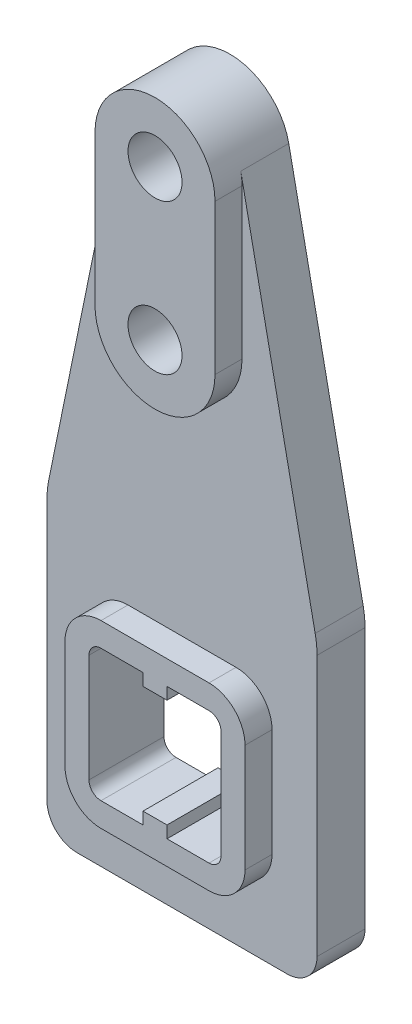
SolidWorks part; units mm, degrees
ref_plane "前视基准面" through (0, 0, 0) normal (0, 0, 1) x (1, 0, 0)
ref_plane "上视基准面" through (0, 0, 0) normal (0, 1, 0) x (1, 0, 0)
ref_plane "右视基准面" through (0, 0, 0) normal (1, 0, 0) x (0, 0, -1)
sketch "草图1" plane through (0, 0, 0) normal (0, 0, 1) x (1, 0, 0)
  line L0 (-161.2654, 0) -> (33.296, 0) construction
  line L1 (35, -50) -> (-35, -50)
  line L2 (45, -40) -> (45, 46.9585)
  line L3 (45, 50) -> (-45, 50)
  line L4 (-45, -40) -> (-45, 46.9585)
  line L5 (45, -50) -> (-45, 50) construction
  line L6 (45, 50) -> (-45, -50) construction
  line L7 (0, 0) -> (0, 71.3082) construction
  line L8 (0, 170) -> (0, 120) construction
  line L9 (20, 170) -> (20, 120)
  line L10 (-20, 170) -> (-20, 120)
  line L11 (-19.0836, 176.5007) -> (-44.3896, 52.9796)
  line L12 (17.866, 182.4439) -> (44.3896, 52.9796)
  arc A0 (20, 170) -> (-20, 170) centre (0, 170) ccw
  arc A1 (-20, 120) -> (20, 120) centre (0, 120) ccw
  circle A2 centre (0, 170) radius 9
  circle A3 centre (0, 120) radius 9
  arc A4 (35, -50) -> (45, -40) centre (35, -40) ccw
  arc A5 (-45, -40) -> (-35, -50) centre (-35, -40) ccw
  arc A6 (45, 46.9585) -> (44.3896, 52.9796) centre (15, 46.9585) ccw
  arc A7 (-45, 46.9585) -> (-44.3896, 52.9796) centre (-15, 46.9585) cw
  point P0 (0, 0)
  point P12 (0, 145)
  dimension "D7" = 18
  dimension "D8" = 18
  dimension "D9" = 10
  dimension "D10" = 30
  dimension "D1" = 90
  dimension "D2" = 100
  dimension "D3" = 40
  dimension "D4" = 50
  dimension "D5" = 120
  dimension "D6" = 0
extrude "凸台-拉伸1" add sketch "草图1" along normal blind 16 contours A7 L4 A5 L1 A4 L2 A6 L3 | A7 L3 A6 L12 A0 L9 A1 L10 L11 region at (0, 0.2272, 0) region at (0, 85.1325, 0)
extrude "凸台-拉伸2" add sketch "草图1<3>" along normal blind 25 contours L10 A1 L9 A0 A3 A2 region at (0, 145, 0)
sketch "草图1<3>" plane through (0, 0, 0) normal (0, 0, 1) x (1, 0, 0) same geometry as "草图1"
sketch "草图2" plane through (0, 0, 0) normal (0, 0, 1) x (1, 0, 0)
  line L1 (18, -30) -> (-18, -30)
  line L2 (30, -18) -> (30, 18)
  line L3 (18, 30) -> (-18, 30)
  line L4 (-30, -18) -> (-30, 18)
  line L5 (30, -30) -> (-30, 30) construction
  line L6 (30, 30) -> (-30, -30) construction
  arc A0 (18, -30) -> (30, -18) centre (18, -18) ccw
  arc A1 (30, 18) -> (18, 30) centre (18, 18) ccw
  arc A2 (-30, -18) -> (-18, -30) centre (-18, -18) ccw
  arc A3 (-30, 18) -> (-18, 30) centre (-18, 18) cw
  point P0 (0, 0)
  dimension "D3" = 12
  dimension "D1" = 60
  dimension "D2" = 60
extrude "凸台-拉伸3" add sketch "草图2" along normal blind 25
sketch "草图3" plane through (0, 0, 25) normal (0, 0, 1) x (1, 0, 0)
  line L0 (-4, 22) -> (-18, 22)
  line L1 (18, -22) -> (4, -22)
  line L2 (22, -18) -> (22, 18)
  line L3 (18, 22) -> (4, 22)
  line L4 (-22, -18) -> (-22, 18)
  line L5 (22, -22) -> (-22, 22) construction
  line L6 (22, 22) -> (-22, -22) construction
  line L7 (-4, -22) -> (-18, -22)
  line L8 (4, -22) -> (4, -18)
  line L9 (4, -18) -> (-4, -18)
  line L10 (-4, -22) -> (-4, -18)
  line L14 (4, 22) -> (4, 18)
  line L15 (4, 18) -> (-4, 18)
  line L16 (-4, 22) -> (-4, 18)
  line L17 (0, 23.1516) -> (-4, 18) construction
  line L18 (4, 18) -> (0, 23.1516) construction
  arc A0 (22, 18) -> (18, 22) centre (18, 18) ccw
  arc A1 (22, -18) -> (18, -22) centre (18, -18) cw
  arc A2 (-22, -18) -> (-18, -22) centre (-18, -18) ccw
  arc A3 (-22, 18) -> (-18, 22) centre (-18, 18) cw
  point P0 (0, 0)
  point P6 (0, -22)
  point P11 (0, 23.1516)
  dimension "D10" = 4
  dimension "D1" = 44
  dimension "D2" = 44
  dimension "D3" = 36
  dimension "D4" = 4
  dimension "D5" = 8
  dimension "D6" = 8
  dimension "D7" = 18
  dimension "D8" = 18
  dimension "D9" = 0
extrude "切除-拉伸1" cut sketch "草图3" against normal blind 25
